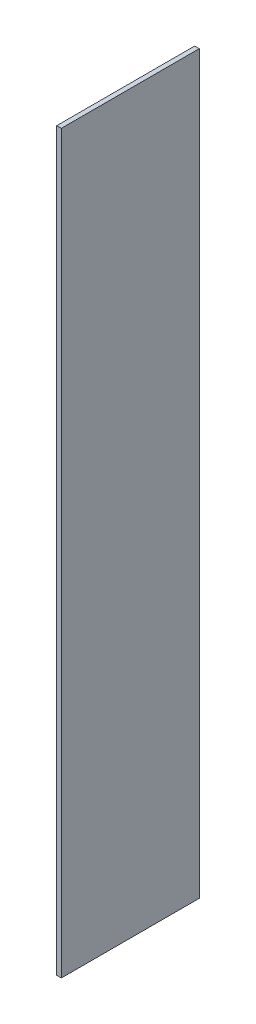
SolidWorks part; units mm, degrees
ref_plane "Front Plane" through (0, 0, 0) normal (0, 0, 1) x (1, 0, 0)
ref_plane "Top Plane" through (0, 0, 0) normal (0, 1, 0) x (1, 0, 0)
ref_plane "Right Plane" through (0, 0, 0) normal (1, 0, 0) x (0, 0, -1)
sketch "Sketch1" plane through (0, 0, 0) normal (0, 0, 1) x (1, 0, 0)
  line L1 (0, 0) -> (0.1, 0)
  line L2 (0, 0) -> (0, 16)
  line L3 (0, 16) -> (0.1, 16)
  line L4 (0.1, 0) -> (0.1, 16)
  dimension "D1" = 16
  dimension "D2" = 0.1
extrude "Boss-Extrude1" add sketch "Sketch1" along normal blind 3
equation "\"A.L\"= 0.07m"
equation "\"A.h\"= 0.007m"
equation "\"A.d\"= 0.003m"
equation "\"A.delta\"= 45.0001"
equation "\"A.w\"= 0.02m"
equation "\"A.v\"= 0.03m"
equation "\"A.s\"= 0.014m"
equation "\"A.t\"= 0.007m"
equation "\"B.L\"= 0.065m"
equation "\"B.h\"= 0.008m"
equation "\"B.s\"= 0.016m"
equation "\"B.t\"= 0.008m"
equation "\"C.h\"= 0.0065m"
equation "\"C.d\"= 0.003m"
equation "\"C.L\"= 0.05m"
equation "\"C.wmax\"= 0.005m"
equation "\"D.L\"= 0.06m"
equation "\"D.h\"= 0.008m"
equation "\"D.s\"= 0.012m"
equation "\"D.t\"= 0.008m"
equation "\"a_h\"= 0.0002m"
equation "\"a_d\"= 0.003m"
equation "\"a_L\"= 0.008m"
equation "\"b_h\"= 0.0004m"
equation "\"b_d\"= 0.003m"
equation "\"b_L\"= 0.007m"
equation "\"c_h\"= 0.0001m"
equation "\"c_d\"= 0.003m"
equation "\"c_L\"= 0.01m"
equation "\"d_h\"= 0.0001m"
equation "\"d_d\"= 0.003m"
equation "\"d_L\"= 0.01m"
equation "\"S.h\"= 0.015m"
equation "\"S.L\"= 0.09075m"
equation "\"D1@Sketch1\"=\"d_L\"+0.006"
equation "\"D2@Sketch1\"=\"d_h\""
equation "\"D1@Boss-Extrude1\"=\"d_d\""
